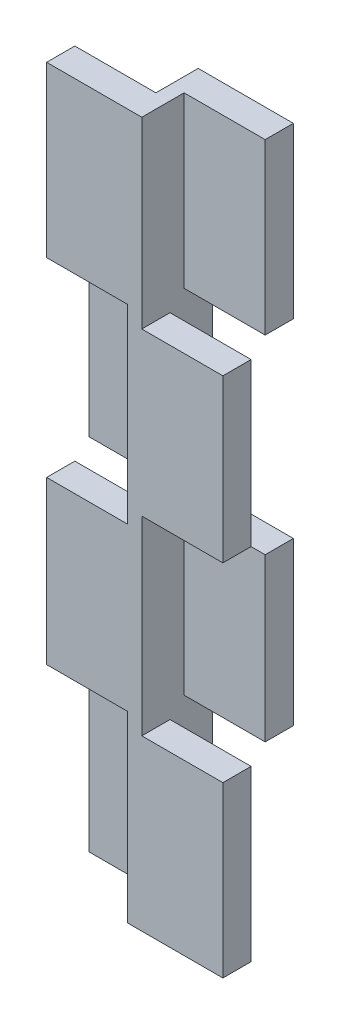
SolidWorks part; units mm, degrees
ref_plane "Front Plane" through (0, 0, 0) normal (0, 0, 1) x (1, 0, 0)
ref_plane "Top Plane" through (0, 0, 0) normal (0, 1, 0) x (1, 0, 0)
ref_plane "Right Plane" through (0, 0, 0) normal (1, 0, 0) x (0, 0, -1)
sketch "Sketch1" plane through (0, 0, 0) normal (0, 0, 1) x (1, 0, 0)
  line L1 (0, 0) -> (0.25, 0)
  line L2 (0, 0) -> (0, 1)
  line L3 (0, 1) -> (0.25, 1)
  line L4 (0.25, 0) -> (0.25, 1)
  dimension "D1" = 0.25
  dimension "D2" = 1
extrude "Boss-Extrude1" add sketch "Sketch1" along normal blind 0.1 contours L2 L3 L4 L1
sketch "Sketch2" plane through (0, 0, 0) normal (-1, 0, 0) x (0, 0, 1)
  line L0 (0.05, 1) -> (0.05, 0) construction
  line L1 (0.1, 1) -> (0, 1) construction
  line L2 (0.1, 0) -> (0, 0) construction
  line L3 (0.04, 1) -> (0.04, 0) construction
  line L4 (0.06, 1) -> (0.06, 0) construction
  line L5 (0, 0.5) -> (0.1, 0.5) construction
  line L6 (0, 0) -> (0, 1) construction
  line L7 (0.1, 0) -> (0.1, 1) construction
  line L8 (0, 0.51) -> (0.1, 0.51) construction
  line L9 (0, 0.49) -> (0.1, 0.49) construction
  line L10 (0, 0.75) -> (0.1, 0.75) construction
  line L11 (0, 0.76) -> (0.1, 0.76) construction
  line L12 (0, 0.74) -> (0.1, 0.74) construction
  line L13 (0, 0.25) -> (0.1, 0.25) construction
  line L14 (0, 0.26) -> (0.1, 0.26) construction
  line L15 (0, 0.24) -> (0.1, 0.24) construction
  line L16 (0.04, 0) -> (0.1, 0)
  line L17 (0.1, 0) -> (0.1, 0.26)
  line L18 (0.1, 0.26) -> (0.06, 0.26)
  line L19 (0.06, 0.26) -> (0.06, 0.49)
  line L20 (0.06, 0.49) -> (0.1, 0.49)
  line L21 (0.1, 0.49) -> (0.1, 0.76)
  line L22 (0.1, 0.76) -> (0.06, 0.76)
  line L23 (0.06, 0.76) -> (0.06, 1)
  line L24 (0.06, 1) -> (0, 1)
  line L25 (0, 1) -> (0, 0.74)
  line L26 (0, 0.74) -> (0.04, 0.74)
  line L27 (0.04, 0.74) -> (0.04, 0.51)
  line L28 (0.04, 0.51) -> (0, 0.51)
  line L29 (0, 0.51) -> (0, 0.24)
  line L30 (0, 0.24) -> (0.04, 0.24)
  line L31 (0.04, 0.24) -> (0.04, 0)
  dimension "D1" = 0.25
  dimension "D2" = 0.25
  dimension "D3" = 0.01
  dimension "D4" = 0.01
  dimension "D5" = 0.01
  dimension "D6" = 0.01
  dimension "D7" = 0.01
  dimension "D8" = 0.01
  dimension "D9" = 0.01
  dimension "D10" = 0.01
extrude "Cut-Extrude1" cut sketch "Sketch2" against normal blind 0.115
sketch "Sketch3" plane through (0.25, 0, 0) normal (1, 0, 0) x (0, 0, -1)
  line L0 (-0.05, 1) -> (-0.05, 0) construction
  line L1 (-0.1, 1) -> (0, 1) construction
  line L2 (-0.1, 0) -> (0, 0) construction
  line L3 (-0.06, 1) -> (-0.06, 0) construction
  line L4 (-0.04, 0) -> (-0.04, 1) construction
  line L5 (-0.1, 0.5) -> (0, 0.5) construction
  line L6 (-0.1, 0) -> (-0.1, 1) construction
  line L7 (0, 0) -> (0, 1) construction
  line L8 (-0.1, 0.51) -> (0, 0.51) construction
  line L9 (0, 0.49) -> (-0.1, 0.49) construction
  line L10 (-0.1, 0.7498) -> (0, 0.7498) construction
  line L11 (-0.1, 0.7398) -> (0, 0.7398) construction
  line L12 (-0.1, 0.7598) -> (0, 0.7598) construction
  line L13 (0, 0.25) -> (-0.1, 0.25) construction
  line L14 (-0.1, 0.26) -> (0, 0.26) construction
  line L15 (-0.04, 1) -> (-0.1, 1)
  line L16 (-0.1, 0.24) -> (0, 0.24) construction
  line L17 (-0.1, 1) -> (-0.1, 0.7398)
  line L18 (-0.1, 0.7398) -> (-0.06, 0.7398)
  line L19 (-0.06, 0.7398) -> (-0.06, 0.51)
  line L20 (-0.06, 0.51) -> (-0.1, 0.51)
  line L21 (-0.1, 0.51) -> (-0.1, 0.24)
  line L22 (-0.1, 0.24) -> (-0.06, 0.24)
  line L23 (-0.06, 0.24) -> (-0.06, 0)
  line L24 (-0.06, 0) -> (0, 0)
  line L25 (0, 0) -> (0, 0.26)
  line L26 (0, 0.26) -> (-0.04, 0.26)
  line L27 (-0.04, 0.26) -> (-0.04, 0.49)
  line L28 (-0.04, 0.49) -> (0, 0.49)
  line L29 (0, 0.49) -> (0, 0.7598)
  line L30 (0, 0.7598) -> (-0.04, 0.7598)
  line L31 (-0.04, 0.7598) -> (-0.04, 1)
  dimension "D3" = 0.01
  dimension "D4" = 0.01
  dimension "D6" = 0.01
  dimension "D7" = 0.01
  dimension "D9" = 0.01
  dimension "D10" = 0.01
  dimension "D1" = 0.01
  dimension "D2" = 0.01
  dimension "D5" = 0.2498
  dimension "D8" = 0.25
extrude "Cut-Extrude2" cut sketch "Sketch3" against normal blind 0.115
equation "\"t\"= 0.25'thickness of the sheets"
equation "\"t_cf\"= 0.115'thickness of single carbon fiber layer"
equation "\"t_kapton\"= 0.025'thickness of single Kapton flex layer"
equation "\"t_fr4\"= 0.1'thickness of FR4 with copper layer"
equation "\"joint_flex\"= 0.1'Width of flextures gap"
equation "\"joint_flex_eff\"= 0.02'Width of flecture after castelation"
equation "\"joint_fold\"= 0.2'Width of folding joints for 90deg fold"
equation "\"gap_tolerance\"= 0.002'Width to have interfecence fit between carbon fiber inserts"
equation "\"assemble_angle\"= 90'Angle of assembly parts"
equation "\"link_lift\"= 0.5'Actuation linkage amplification for the lift motion"
equation "\"link_swing\"= 0.45'Actuation linkage amplification for the swing motion"
equation "\"D1@Sketch1\"=\"t\""
equation "\"D1@Boss-Extrude1\"=\"joint_flex\""
equation "\"fold_gap\"= 0.01"
equation "\"D3@Sketch2\"=\"joint_flex_eff\"/2"
equation "\"D4@Sketch2\"=\"joint_flex_eff\"/2"
equation "\"D5@Sketch2\"=\"fold_gap\""
equation "\"D6@Sketch2\"=\"fold_gap\""
equation "\"D7@Sketch2\"=\"fold_gap\""
equation "\"D8@Sketch2\"=\"fold_gap\""
equation "\"D9@Sketch2\"=\"fold_gap\""
equation "\"D10@Sketch2\"=\"fold_gap\""
equation "\"D1@Cut-Extrude1\"=\"t_cf\""
equation "\"D1@Sketch3\"=\"joint_flex_eff\"/2"
equation "\"D2@Sketch3\"=\"joint_flex_eff\"/2"
equation "\"D3@Sketch3\"=\"fold_gap\""
equation "\"D4@Sketch3\"=\"fold_gap\""
equation "\"D6@Sketch3\"=\"fold_gap\""
equation "\"D7@Sketch3\"=\"fold_gap\""
equation "\"D9@Sketch3\"=\"fold_gap\""
equation "\"D10@Sketch3\"=\"fold_gap\""
equation "\"D1@Cut-Extrude2\"=\"t_cf\""
